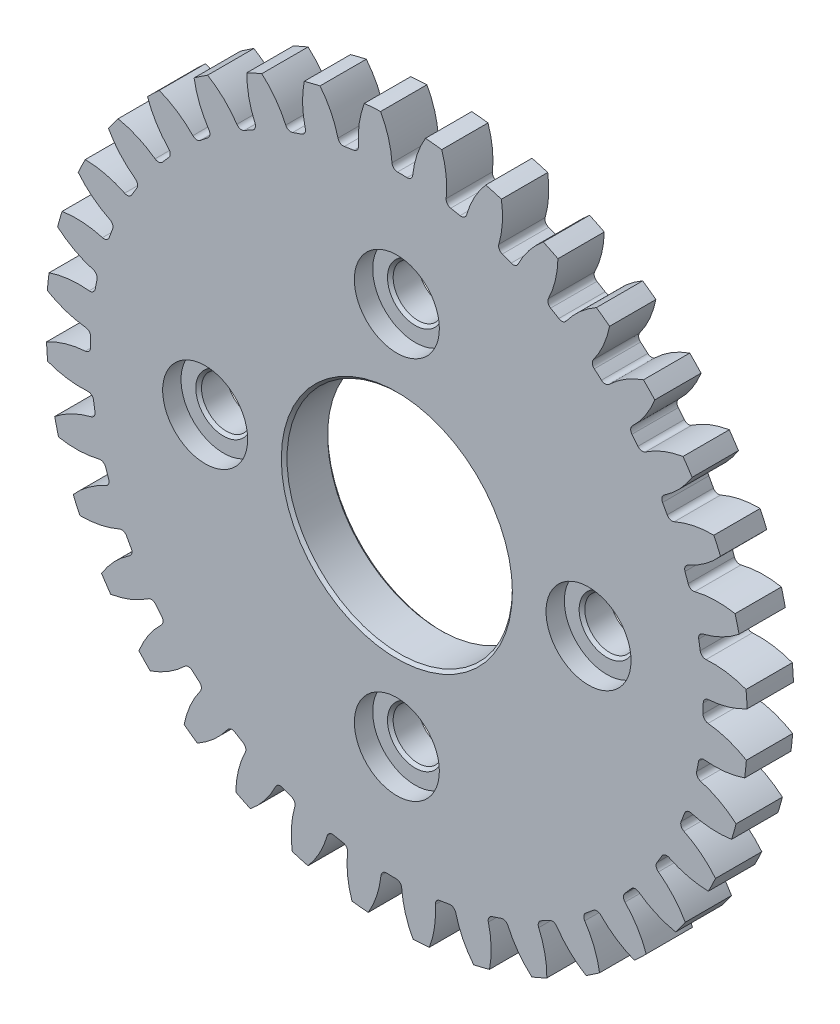
SolidWorks part; units mm, degrees
ref_plane "Front Plane" through (0, 0, 0) normal (0, 0, 1) x (1, 0, 0)
ref_plane "Top Plane" through (0, 0, 0) normal (0, 1, 0) x (1, 0, 0)
ref_plane "Right Plane" through (0, 0, 0) normal (1, 0, 0) x (0, 0, -1)
sketch "Sketch1" plane through (0, 0, 0) normal (0, 0, 1) x (1, 0, 0)
  circle A0 centre (0, 0) radius 23.4
  circle A1 centre (0, 0) radius 24.7
  circle A2 centre (0, 0) radius 21.58
  dimension "D1" = 46.8
  dimension "D2" = 49.4
  dimension "D3" = 3.12
extrude "Boss-Extrude1" add sketch "Sketch1" along normal mid plane 3.2607 contours A2 | A0 A2 | A1 A0 region at (-22.7381, 0, 0) region at (-24.0014, 0, 0) region at (0, 0, 0)
sketch "Sketch3" plane through (0, 0, 1.6304) normal (0, 0, 1) x (1, 0, 0)
  line L0 (0, 0) -> (0, 24.7) construction
  line L1 (-1.0207, 23.3777) -> (1.0207, 23.3777) construction
  line L2 (0, 0) -> (-0.7079, 21.5684) construction
  line L3 (0, 20.5885) -> (-1.8365, 25.6343) construction
  line L4 (0, 0) -> (2.1527, 24.606) construction
  line L5 (1.0207, 23.3777) -> (3.0543, 23.1998) construction
  circle A0 centre (0, 0) radius 24.7 construction
  arc A1 (-2.2399, 25.6022) -> (-0.7079, 21.5684) centre (-7.3591, 21.3501) cw
  arc A2 (2.2399, 25.6022) -> (0.7079, 21.5684) centre (7.3591, 21.3501) ccw
  circle A3 centre (0, 0) radius 21.58 construction
  arc A4 (0.7079, 21.5684) -> (-0.7079, 21.5684) centre (0, 0) ccw
  circle A6 centre (0, 0) radius 23.4 construction
  circle A7 centre (0, 0) radius 25.7
  arc A8 (2.2399, 25.6022) -> (-2.2399, 25.6022) centre (0, 0) ccw
  circle A9 centre (0, 0) radius 24.7 construction
  point P20 (2.0375, 23.2888)
  dimension "D2" = 20
  dimension "D3" = 5
sketch "Sketch4" plane through (0, 0, 0) normal (0, 1, 0) x (1, 0, 0)
  line L0 (0.4369, -1.6304) -> (-0.4369, 1.6304)
  line L1 (-24.7, -1.6304) -> (24.7, -1.6304) construction
  line L2 (24.7, 1.6304) -> (-24.7, 1.6304) construction
  line L3 (0, -3.1031) -> (0, 3.1031) construction
  dimension "D1" = 15
curve "Curve1"
sketch "Sketch5" plane through (0, 0, 1.6304) normal (0, 0, 1) x (0.9998, -0.0177, 0)
  line L0 (0, 0) -> (0, 24.7) construction
  line L1 (-1.0207, 23.3777) -> (1.0207, 23.3777) construction
  line L2 (0, 0) -> (-0.7079, 21.5684) construction
  line L3 (0, 20.5885) -> (-1.8365, 25.6343) construction
  line L4 (0, 0) -> (2.1527, 24.606) construction
  line L5 (1.0207, 23.3777) -> (3.0543, 23.1998) construction
  arc A1 (-2.2399, 25.6022) -> (-0.7079, 21.5684) centre (-7.3591, 21.3501) cw
  arc A2 (2.2399, 25.6022) -> (0.7079, 21.5684) centre (7.3591, 21.3501) ccw
  arc A4 (0.7079, 21.5684) -> (-0.7079, 21.5684) centre (0, 0) ccw
  arc A8 (2.2399, 25.6022) -> (-2.2399, 25.6022) centre (0, 0) ccw
  point P20 (2.0375, 23.2888)
sketch "Sketch7" [suppressed] plane through (1.6622, 0.2826, -4.7625) normal (0, 0, 1) x (0.9724, 0.2332, 0)
  line L0 (0, 0) -> (0, 12.6) construction
  line L1 (-1.4097, 10.7076) -> (1.4097, 10.7076) construction
  line L2 (0, 0) -> (-0.707, 8.2498) construction
  line L3 (0, 6.9803) -> (-2.3358, 13.3979) construction
  line L4 (0, 0) -> (3.2611, 12.1707) construction
  line L5 (1.4097, 10.7076) -> (4.133, 9.9779) construction
  arc A1 (-3.5199, 13.1366) -> (-0.707, 8.2498) centre (-7.3467, 7.6808) cw
  arc A2 (3.5199, 13.1366) -> (0.707, 8.2498) centre (7.3467, 7.6808) ccw
  arc A4 (0.707, 8.2498) -> (-0.707, 8.2498) centre (0, 0) ccw
  arc A8 (3.5199, 13.1366) -> (-3.5199, 13.1366) centre (0, 0) ccw
  point P20 (2.7713, 10.3428)
loft "Cut-Loft1" [suppressed] cut profiles "Sketch7", "Sketch3" end constraint default
fillet "Fillet2" [suppressed] radius 0.39
pattern_circular "CirPattern2" [suppressed] count 36 over 360 of bodies 104
sketch "Sketch8" plane through (0, 0, 1.6304) normal (0, 0, 1) x (1, 0, 0)
  line L0 (0, 24.7) -> (0, -24.7) construction
  line L1 (0, 0) -> (7.9375, 0) construction
  circle A0 centre (0, 0) radius 7.9375
  circle A1 centre (0, 0) radius 24.7 construction
  circle A2 centre (0, 13.5) radius 1.7526
  circle A3 centre (13.5, 0) radius 1.7526
  circle A4 centre (0, -13.5) radius 1.7526
  circle A5 centre (-13.5, 0) radius 1.7526
  spline S0 degree 3 poles (-0.4369, 24.6961) (-0.1456, 24.7013) (0.1456, 24.7013) (0.4369, 24.6961) knots 0 0 0 0 1 1 1 1 weights 1 0.999896 0.999896 1 construction
  point P26 (0, 0)
  dimension "D1" = 15.875
  dimension "D2" = 13.5
  dimension "D3" = 3.5052
  dimension "D4" = 4
extrude "Cut-Extrude1" cut sketch "Sketch8" against normal through all
extrude "Cut-Extrude2" cut sketch "Sketch5" against normal through all
fillet "Fillet3" radius 0.39 2 edges at (-0.3263, 21.5775, 0) (1.0892, 21.5525, 0)
pattern_circular "CirPattern3" count 36 over 360 about axis through (0, 0, 1.6304) along (0, 0, -1) of "Cut-Extrude2", "Fillet3"
sketch "Sketch9" plane through (0, 0, 1.6304) normal (0, 0, 1) x (1, 0, 0)
  line L0 (0, 0) -> (0, 11.1125) construction
  line L1 (0, 0) -> (11.1125, 0) construction
  circle A0 centre (0, 0) radius 11.1125 construction
  circle A1 centre (0, 0) radius 19.05 construction
  circle A2 centre (0, 13.5) radius 2.994
  circle A3 centre (13.5, 0) radius 2.994
  circle A4 centre (0, -13.5) radius 2.994
  circle A5 centre (-13.5, 0) radius 2.994
  point P23 (0, 0)
  dimension "D1" = 22.225
  dimension "D3" = 5.988
  dimension "D2" = 7.9375
  dimension "D4" = 4
extrude "Cut-Extrude3" cut sketch "Sketch9" against normal blind 1.292
chamfer "Chamfer1" distance 0.2 angle 45 6 edges at (7.9375, 0, 1.6304) (7.9375, 0, -1.6304) (-11.7474, 0, 0.3384) (1.7526, -13.5, 0.3384) (15.2526, 0, 0.3384) (1.7526, 13.5, 0.3384)
sketch "Sketch10" plane through (0, 0, 1.6304) normal (0, 0, 1) x (1, 0, 0)
  line L0 (0, 0) -> (2.5876, 24.5641) construction
  line L1 (0, 0) -> (6.8138, 23.7416) construction
  line L2 (2.5876, 24.5641) -> (14.5565, 23.3033) construction
  line L3 (2.5876, 24.5641) -> (8.0644, 24.5641) construction
  line L4 (-1.1435, 24.6735) -> (2.3134, 24.9144) construction
  line L5 (-1.1435, 24.6735) -> (1.7618, 24.6735) construction
  line L6 (-2.6498, 23.2082) -> (-0.595, 23.3514) construction
  arc A0 (5.9526, 20.7409) -> (2.2606, 21.4595) centre (0, 0) ccw construction
  arc A1 (3.1584, 24.4972) -> (2.0155, 24.6176) centre (0, 0) ccw construction
  arc A2 (7.3643, 23.5766) -> (6.2596, 23.8937) centre (0, 0) ccw construction
  arc A3 (2.5876, 24.5641) -> (6.8138, 23.7416) centre (0, 0) cw construction
  arc A5 (-2.29, 24.5936) -> (-2.7051, 21.778) centre (3.9338, 22.2375) ccw construction
  arc A6 (-0.3418, 21.9427) -> (-1.1435, 24.6735) centre (-6.9803, 21.4769) ccw construction
  dimension "D1" = 3.987
equation "\"Module\"= 1.3mm"
equation "\"Number of Teeth\"= 36"
equation "\"D1@Sketch1\"=\"Module\" * \"Number of Teeth\""
equation "\"D2@Sketch1\"=(\"Number of Teeth\" + 2) * \"Module\""
equation "\"D3@Sketch1\"=\"Module\" * if(  \"Module\" => 1.25, 2.25, 2.4)"
equation "\"D3@Sketch3\"=180 / \"Number of Teeth\""
equation "\"D1@Fillet2\"= \"Module\" * 0.3"
equation "\"D1@CirPattern2\"= \"Number of Teeth\""
equation "\"D1@Fillet3\"=\"Module\"*.3"
equation "\"D1@CirPattern3\"=\"Number of Teeth\""
